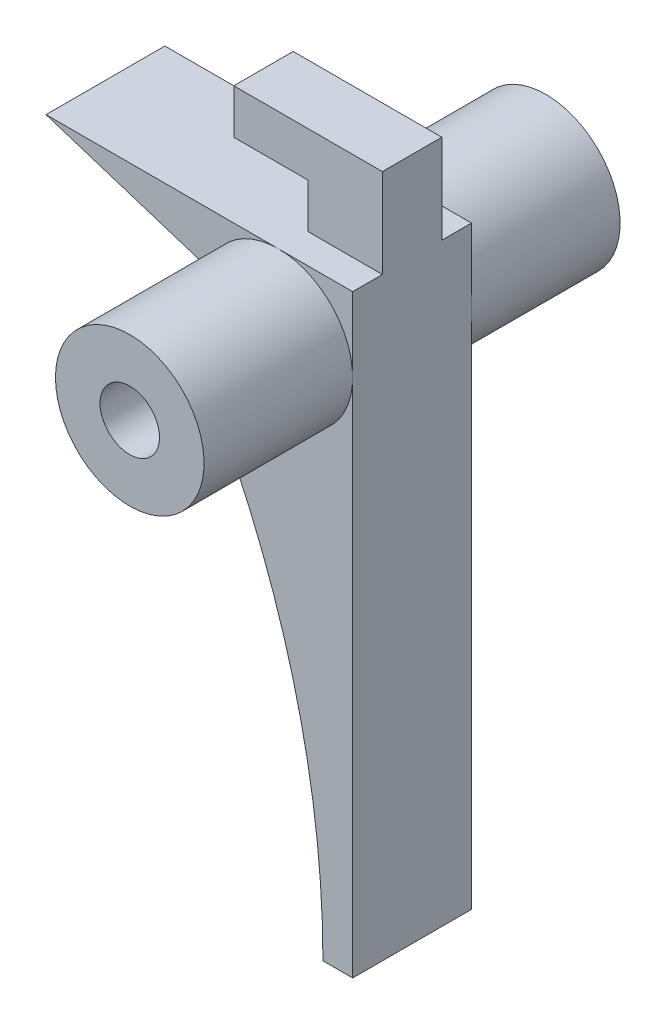
SolidWorks part; units mm, degrees
ref_plane "Alzado" through (0, 0, 0) normal (0, 0, 1) x (1, 0, 0)
ref_plane "Planta" through (0, 0, 0) normal (0, 1, 0) x (1, 0, 0)
ref_plane "Vista lateral" through (0, 0, 0) normal (1, 0, 0) x (0, 0, -1)
sketch "Croquis1" plane through (0, 0, 0) normal (0, 0, 1) x (1, 0, 0)
  line L0 (-5, -5) -> (3, -35) construction
  line L1 (-5, 5) -> (5, 5)
  line L2 (-5, 1.5989) -> (-5, -5)
  line L4 (5, 5) -> (5, -5)
  line L5 (-5, 5) -> (5, -5) construction
  line L6 (-5, -5) -> (5, 5) construction
  line L7 (3, -35) -> (5, -35)
  line L10 (5, -35) -> (5, -5)
  line L11 (3, -35) -> (5, -5) construction
  line L12 (4, -20) -> (5, -35) construction
  line L13 (-1, -20) -> (-57.25, -35) construction
  line L14 (-57.25, -35) -> (3, -35) construction
  line L22 (-15.6355, 5) -> (-5, 5)
  line L24 (-5, 1.5989) -> (-15.6355, 5)
  arc A0 (3, -35) -> (-5, -5) centre (-57.25, -35) ccw
  circle A1 centre (0, 0) radius 2
  point P0 (0, 0)
  point P6 (4, -20)
  point P14 (-15.6355, 3.6315)
  dimension "D5" = 4
  dimension "D1" = 10
  dimension "D2" = 10
  dimension "D3" = 30
  dimension "D4" = 2
extrude "Saliente-Extruir1" add sketch "Croquis1" along normal blind 8
sketch "Croquis3" plane through (0, 0, 0) normal (0, 0, -1) x (-1, 0, 0)
  circle A0 centre (0, 0) radius 5
extrude "Saliente-Extruir2" add sketch "Croquis3" along normal blind 10 and the other way blind 18
sketch "Croquis4" plane through (0, 0, -10) normal (0, 0, -1) x (-1, 0, 0)
  circle A0 centre (0, 0) radius 2
  dimension "D1" = 4
extrude "Cortar-Extruir1" cut sketch "Croquis4" against normal up to surface (28 mm away) up to face at (-5, 0, 18)
sketch "Croquis5" plane through (0, 5, 0) normal (0, 1, 0) x (1, 0, 0)
  line L0 (-15.6355, -4) -> (5, -4) construction
  line L1 (-15.6355, -8) -> (-15.6355, 0) construction
  line L2 (5, -8) -> (5, 0) construction
  line L4 (0, -6) -> (5, -6)
  line L5 (0, -6) -> (0, -2)
  line L6 (0, -2) -> (5, -2)
  line L7 (5, -6) -> (5, -2)
  line L8 (0, -6) -> (5, -2) construction
  line L9 (0, -2) -> (5, -6) construction
  point P6 (2.5, -4)
  dimension "D1" = 5
  dimension "D2" = 4
extrude "Saliente-Extruir3" add sketch "Croquis5" along normal blind 3
sketch "Croquis6" plane through (0, 8, 0) normal (0, 1, 0) x (1, 0, 0)
  line L0 (0, -2) -> (0, -6) construction
  line L1 (-5, -6) -> (5, -6)
  line L2 (-5, -6) -> (-5, -2)
  line L3 (-5, -2) -> (5, -2)
  line L4 (5, -6) -> (5, -2)
  line L5 (-5, -6) -> (5, -2) construction
  line L6 (-5, -2) -> (5, -6) construction
  point P0 (0, -4)
extrude "Saliente-Extruir4" add sketch "Croquis6" along normal blind 3
ref_axis "Eje1" through (0, 0, 18) along (0, 0, -1)
sketch "Croquis7" plane through (0, 0, 18) normal (0, 0, 1) x (1, 0, 0)
  line L0 (-0.9473, 15.783) -> (-8.7119, -13.1948) construction
  line L1 (-18.3712, -10.6066) -> (-10.6066, 18.3712) construction
  line L2 (-18.3712, -10.6066) -> (-8.7119, -13.1948) construction
  line L3 (10.6066, -18.3712) -> (18.3712, 10.6066) construction
  line L4 (-10.6066, 18.3712) -> (-0.9473, 15.783) construction
  line L5 (-15, 15) -> (15, -15) construction
  line L6 (-15, -15) -> (15, 15) construction
  line L9 (8.7119, 13.1948) -> (0.9473, -15.783) construction
  line L10 (0.9473, -15.783) -> (10.6066, -18.3712) construction
  line L11 (8.7119, 13.1948) -> (18.3712, 10.6066) construction
  circle A0 centre (0, 0) radius 15 construction
  dimension "D1" = 30
  dimension "D2" = 30
  dimension "D3" = 30
  dimension "D4" = 10
  dimension "D5" = 10
